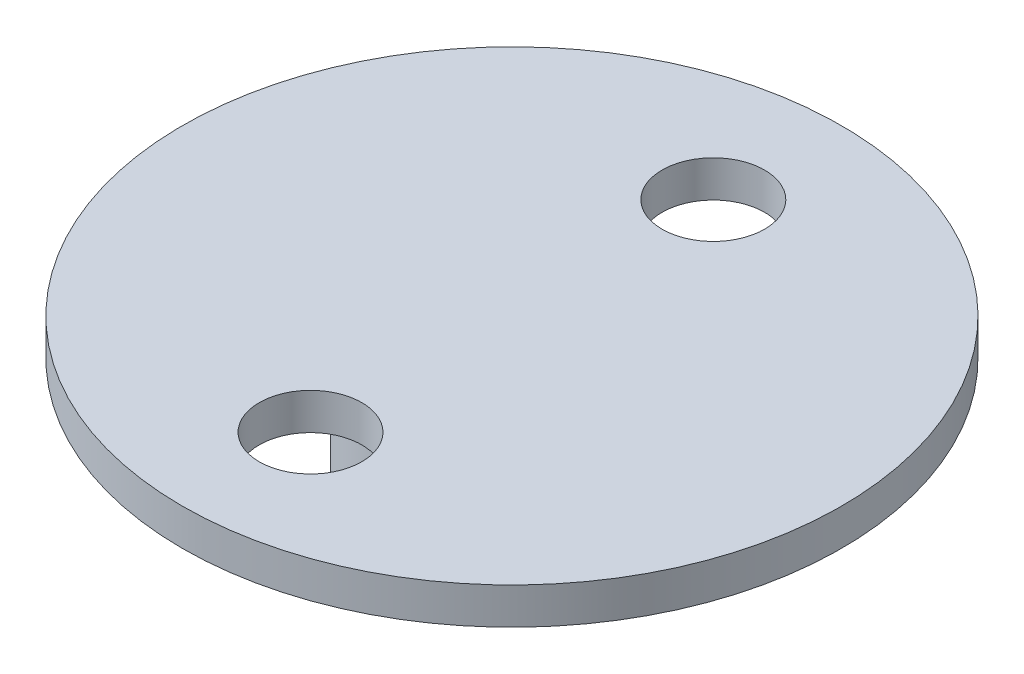
SolidWorks part; units mm, degrees
ref_plane "Front Plane" through (0, 0, 0) normal (0, 0, 1) x (1, 0, 0)
ref_plane "Top Plane" through (0, 0, 0) normal (0, 1, 0) x (1, 0, 0)
ref_plane "Right Plane" through (0, 0, 0) normal (1, 0, 0) x (0, 0, -1)
sketch "Sketch1" plane through (0, 0, 0) normal (0, 1, 0) x (1, 0, 0)
  circle A0 centre (0, 0) radius 9
  arc A1 (8.9914, 0.3938) -> (-8.9914, 0.3938) centre (0, 0) ccw construction
extrude "Boss-Extrude1" add sketch "Sketch1" against normal blind 1
sketch "Sketch2" plane through (0, 0, 0) normal (0, 1, 0) x (1, 0, 0)
  circle A0 centre (0, -5.5) radius 1.4 construction
  circle A1 centre (0, 5.5) radius 1.4 construction
  circle A2 centre (0, -5.5) radius 1.4
  circle A3 centre (0, 5.5) radius 1.4
extrude "Cut-Extrude1" cut sketch "Sketch2" against normal through all
sketch "Sketch3" plane through (0, -1, 0) normal (0, -1, 0) x (1, 0, 0)
  line L0 (1.9074, 1.6161) -> (2.0855, -1.3786) construction
  line L1 (1.9074, 1.6161) -> (2.0855, -1.3786) construction
  line L2 (1.9857, 1.6472) -> (2.1669, -1.4003)
  arc A0 (1.9074, 1.6161) -> (2.0855, -1.3786) centre (0, 0) ccw construction
  arc A1 (1.9074, 1.6161) -> (2.0855, -1.3786) centre (0, 0) ccw construction
  arc A2 (1.9857, 1.6472) -> (2.1669, -1.4003) centre (0, 0) ccw
  circle A3 centre (0, 0) radius 3.5
  dimension "D2" = 7
  dimension "D1" = 2.58
extrude "Boss-Extrude2" add sketch "Sketch3" along normal blind 3.5
fillet "Fillet1" radius 0.5 2 edges at (2.0763, -4.5, 0.1235) (-2.5755, -4.5, -0.1531)
